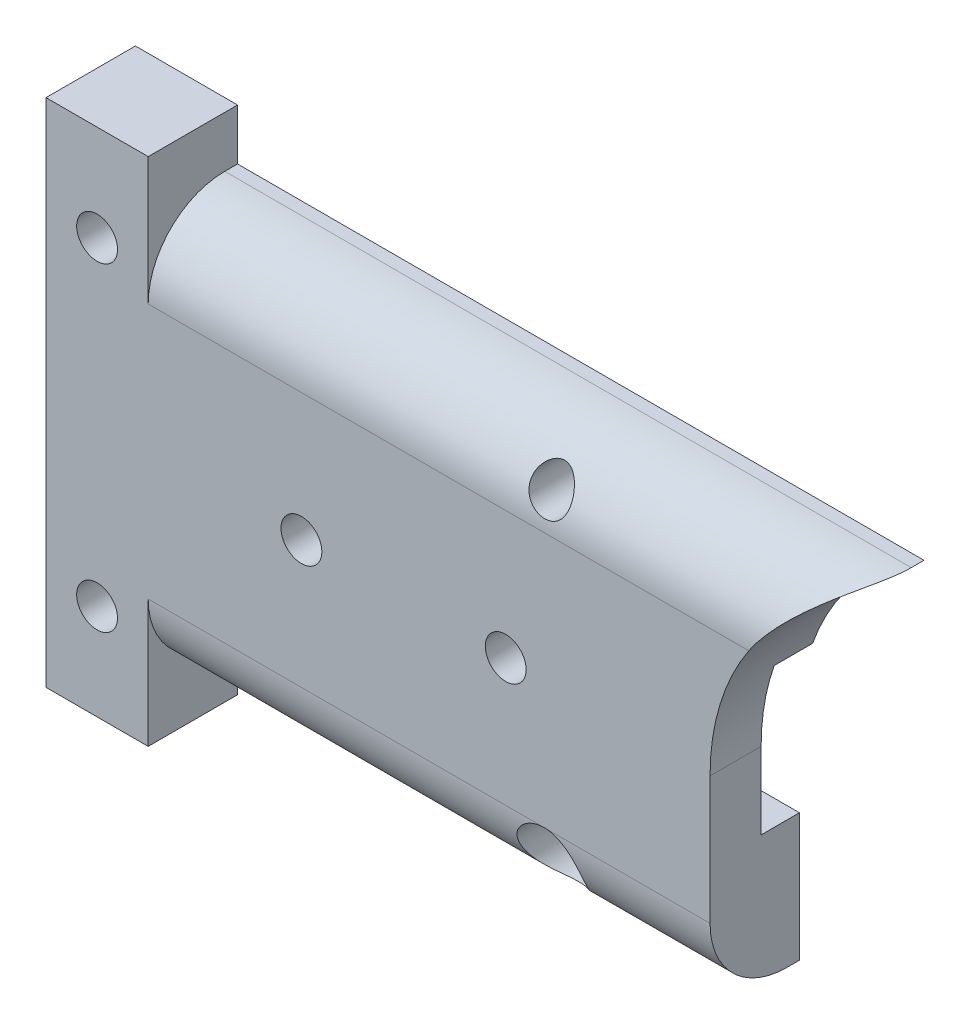
SolidWorks part; units mm, degrees
ref_plane "Front Plane" through (0, 0, 0) normal (0, 0, 1) x (1, 0, 0)
ref_plane "Top Plane" through (0, 0, 0) normal (0, 1, 0) x (1, 0, 0)
ref_plane "Right Plane" through (0, 0, 0) normal (1, 0, 0) x (0, 0, -1)
sketch "Sketch1" plane through (0, 0, 0) normal (0, 0, 1) x (1, 0, 0)
  line L0 (45.1613, 0) -> (10.1613, 0) construction
  line L1 (10.1613, 0) -> (10.1613, 8)
  line L2 (10.1613, 0) -> (10.1613, -8)
  line L3 (10.1613, 8) -> (41.0382, 8)
  line L4 (10.1613, -8) -> (41.0382, -8)
  line L5 (36.1613, 0) -> (36.1613, -8)
  line L6 (10.1613, 8) -> (10.1613, 10)
  line L7 (10.1613, 10) -> (14.1613, 10)
  line L8 (14.1613, 10) -> (14.1613, 8)
  line L9 (10.1613, -8) -> (10.1613, -10)
  line L10 (10.1613, -10) -> (14.1613, -10)
  line L11 (14.1613, -10) -> (14.1613, -8)
  circle A0 centre (45.1613, 0) radius 9
extrude "Boss-Extrude1" add sketch "Sketch1" along normal blind 3.5 contours L0 A0 L1 | L0 L2 | L8 L7 L6 L3 | L10 L11 L4 L9 region at (23.1613, -4, 0) region at (23.8925, 4.1082, 0) region at (12.1613, 9, 0) region at (12.1613, -9, 0)
sketch "Sketch3" plane through (0, 0, 0) normal (0, 0, 1) x (1, 0, 0)
  line L0 (10.1613, 3) -> (10.1613, 0)
  line L2 (10.1613, 3) -> (38.2874, 3)
  line L3 (38.2874, 3) -> (38.2874, -3)
  line L4 (38.2874, -3) -> (10.1613, -3)
  line L5 (10.1613, -10) -> (10.1613, 10) construction
  line L6 (10.1613, 0) -> (10.1613, -3)
  line L7 (10.1613, 0) -> (38.2874, 0) construction
extrude "Wire Canal" cut sketch "Sketch3" along normal blind 1.5
sketch "Sketch2" plane through (0, 0, 0) normal (0, 0, 1) x (1, 0, 0)
  line L0 (10.1613, 0) -> (12.1613, 0) construction
  line L1 (12.1613, 0) -> (12.1613, 6.25) construction
  line L2 (10.1613, 0) -> (20.1613, 0) construction
  line L3 (12.1613, 0) -> (12.1613, -6.25) construction
  line L4 (12.1613, 0) -> (29.6613, 0) construction
  line L5 (29.6613, 0) -> (29.6613, 6.25) construction
  line L6 (29.6613, 0) -> (29.6613, -6.25) construction
  line L7 (10.1613, 8) -> (10.1613, 0) construction
  line L8 (12.1613, 0) -> (28.1613, 0) construction
  line L9 (20.1613, 0) -> (28.1613, 0) construction
  circle A0 centre (20.1613, 0) radius 0.8
  circle A1 centre (12.1613, -6.25) radius 0.8
  circle A2 centre (29.6613, 6.25) radius 0.8
  circle A3 centre (29.6613, -6.25) radius 0.8
  circle A4 centre (12.1613, 6.25) radius 0.8
  circle A5 centre (28.1613, 0) radius 0.8
extrude "Screw Holes" cut sketch "Sketch2" along normal through all
fillet "Fillet1" radius 3 2 edges at (25.1613, -8, 3.5) (27.5997, 8, 3.5)
sketch "Sketch4" plane through (0, 0, 0) normal (0, 0, 1) x (1, 0, 0)
  circle A0 centre (29.6613, -6.25) radius 1.25
extrude "Cut-Extrude1" cut sketch "Sketch4" against normal blind 3 from offset 3.5
